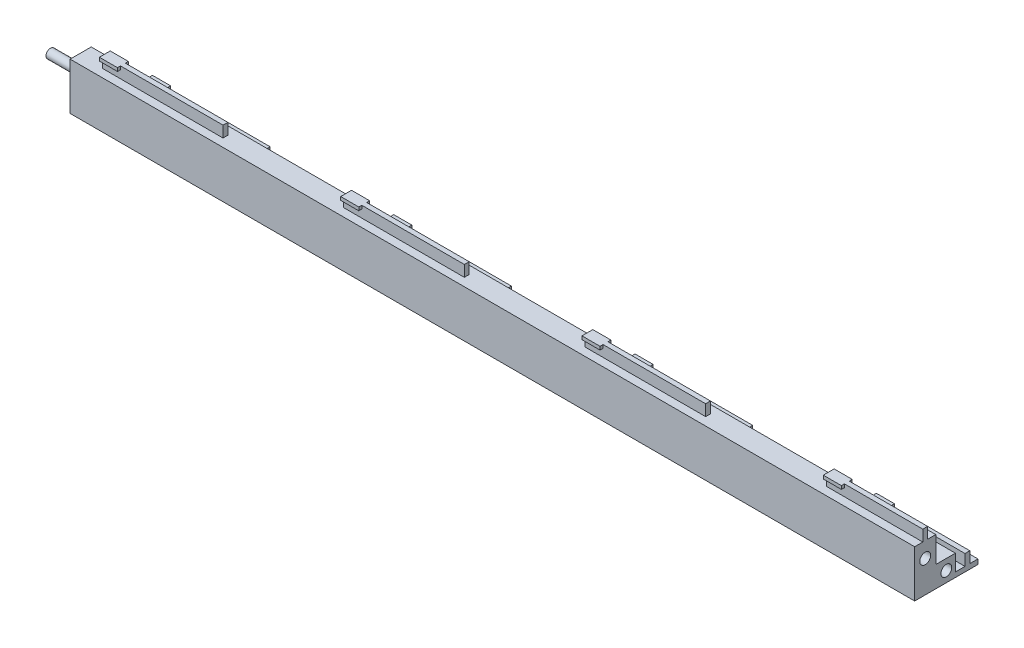
SolidWorks part; units mm, degrees
ref_plane "Front Plane" through (0, 0, 0) normal (0, 0, 1) x (1, 0, 0)
ref_plane "Top Plane" through (0, 0, 0) normal (0, 1, 0) x (1, 0, 0)
ref_plane "Right Plane" through (0, 0, 0) normal (1, 0, 0) x (0, 0, -1)
sketch "Sketch1" plane through (-58.1463, 0, 0) normal (1, 0, 0) x (0, 0, -1)
  line L1 (-13.5289, 87.3403) -> (-24.0289, 87.3403)
  line L2 (-50.0289, 87.3403) -> (-18.5289, 87.3403) construction
  line L3 (-24.0289, 87.3403) -> (-24.0289, 76.8403)
  line L4 (-24.0289, 76.8403) -> (-13.5289, 76.8403)
  line L5 (-13.5289, 82.3403) -> (-13.5289, 22.3403) construction
  line L7 (-13.5289, 76.8403) -> (-13.5289, 87.3403)
  line L8 (-20.5289, 87.3403) -> (-20.5289, 80.3403)
  line L9 (-20.5289, 80.3403) -> (-13.5289, 80.3403)
  line L10 (-24.0289, 84.6403) -> (-22.6789, 84.6403)
  line L11 (-22.6789, 84.6403) -> (-22.6789, 85.9403)
  line L12 (-22.6789, 85.9403) -> (-23.1789, 85.9403)
  line L13 (-23.1789, 85.9403) -> (-23.1789, 86.4903)
  line L14 (-23.1789, 86.4903) -> (-21.3789, 86.4903)
  line L15 (-21.3789, 86.4903) -> (-21.3789, 85.9403)
  line L16 (-21.3789, 85.9403) -> (-21.8789, 85.9403)
  line L17 (-21.8789, 85.9403) -> (-21.8789, 84.6403)
  line L18 (-21.8789, 84.6403) -> (-20.5289, 84.6403)
  line L19 (-17.0289, 77.6403) -> (-15.6789, 77.6403)
  line L20 (-15.6789, 77.6403) -> (-15.6789, 78.9403)
  line L21 (-15.6789, 78.9403) -> (-16.1789, 78.9403)
  line L22 (-16.1789, 78.9403) -> (-16.1789, 79.4903)
  line L23 (-16.1789, 79.4903) -> (-14.3789, 79.4903)
  line L24 (-14.3789, 79.4903) -> (-14.3789, 78.9403)
  line L25 (-14.3789, 78.9403) -> (-14.8789, 78.9403)
  line L26 (-14.8789, 78.9403) -> (-14.8789, 77.6403)
  line L27 (-14.8789, 77.6403) -> (-13.5289, 77.6403)
  line L28 (-24.0289, 83.8403) -> (-20.5289, 83.8403)
  line L29 (-17.0289, 80.3403) -> (-17.0289, 76.8403)
  line L30 (-17.0289, 76.8403) -> (-13.3587, 76.8403)
  circle A0 centre (-22.2789, 82.0903) radius 0.75
  circle A1 centre (-18.7789, 78.5903) radius 0.75
  circle A2 centre (-22.2789, 82.0903) radius 0.9
  circle A3 centre (-18.7789, 78.5903) radius 0.9
  point P18 (-12.6276, 76.5275)
  point P42 (0, 0)
  point P45 (0, 0)
  point P46 (-13.9157, 77.8122)
  line M11 (-13.5289, 22.3403) -> (-13.5289, 82.3403)
  dimension "D5" = 1.5
  dimension "D6" = 1.8
  dimension "D7" = 1.5
  dimension "D8" = 1.8
  dimension "D1" = 10.5
  dimension "D2" = 10.5
  dimension "D3" = 1.75
  dimension "D4" = 5.25
  dimension "D9" = 1.75
  dimension "D10" = 5.25
  dimension "D11" = 3.5
  dimension "D12" = 3.5
  dimension "D13" = 0.85
  dimension "D14" = 0.55
  dimension "D15" = 0.55
  dimension "D16" = 0.55
  dimension "D17" = 1.3
  dimension "D18" = 1.3
  dimension "D19" = 1.35
  dimension "D20" = 1.35
  dimension "D21" = 0.55
  dimension "D22" = 1.3
  dimension "D23" = 1.3
  dimension "D24" = 0.85
  dimension "D25" = 0.85
  dimension "D26" = 0.85
  dimension "D27" = 0.85
  dimension "D28" = 0.85
  dimension "D29" = 1.35
  dimension "D30" = 1.35
  dimension "D31" = 3.5
  dimension "D32" = 3.5
extrude "Boss-Extrude1" add sketch "Sketch1" along normal blind 140 contours L29 L9 L8 L28 L3 L4 L20 A3 A2 | A0 | A2 A0 | A1 | A3 A1 | L3 L28 L8 L18 L17 L16 L15 L14 L13 L12 L11 L10 | L19 L29 L4 L27 L26 L25 L24 L23 L22 L21 L20 M11 region at (-58.1463, 84.8712, 22.2789) region at (-58.1463, 79.6632, 21.206) region at (-58.1463, 77.8712, 15.2789) region at (-58.1463, 82.0903, 22.2789) region at (-58.1463, 78.5903, 18.7789) region at (-58.1463, 82.0903, 23.1534) region at (-58.1463, 78.5903, 19.6534)
extrude "Boss-Extrude2" add sketch "Sketch1<5>" against normal blind 5 contours A0 | A1 region at (-58.1463, 82.0903, 22.2789) region at (-58.1463, 78.5903, 18.7789)
sketch "Sketch1<5>" plane through (-58.1463, 0, 0) normal (1, 0, 0) x (0, 0, -1) same geometry as "Sketch1"
sketch "Sketch2" plane through (81.8537, 0, 0) normal (1, 0, 0) x (0, 0, -1)
  line L0 (-13.5289, 87.3403) -> (-24.0289, 87.3403)
  line L1 (-24.0289, 87.3403) -> (-24.0289, 76.8403)
  line L2 (-24.0289, 76.8403) -> (-13.5289, 76.8403)
  line L3 (-13.5289, 76.8403) -> (-13.5289, 87.3403)
  line L4 (-20.5289, 87.3403) -> (-20.5289, 80.3403)
  line L5 (-20.5289, 80.3403) -> (-13.5289, 80.3403)
  line L6 (-24.0289, 84.8403) -> (-22.7789, 84.8403)
  line L7 (-22.7789, 84.8403) -> (-22.7789, 85.8403)
  line L8 (-22.7789, 85.8403) -> (-23.5289, 85.8403)
  line L9 (-23.5289, 85.8403) -> (-23.5289, 86.5903)
  line L10 (-23.5289, 86.5903) -> (-21.0289, 86.5903)
  line L11 (-21.0289, 86.5903) -> (-21.0289, 85.8403)
  line L12 (-21.0289, 85.8403) -> (-21.7789, 85.8403)
  line L13 (-21.7789, 85.8403) -> (-21.7789, 84.8403)
  line L14 (-21.7789, 84.8403) -> (-20.5289, 84.8403)
  line L15 (-15.9289, 80.3403) -> (-15.9289, 78.4903)
  line L16 (-15.9289, 78.4903) -> (-17.0289, 78.4903)
  line L17 (-17.0289, 78.4903) -> (-17.0289, 77.5903)
  line L18 (-17.0289, 77.5903) -> (-13.5289, 77.5903)
  line L19 (-13.5289, 77.5903) -> (-13.5289, 78.4903)
  line L20 (-13.5289, 78.4903) -> (-14.6289, 78.4903)
  line L21 (-14.6289, 78.4903) -> (-14.6289, 80.3403)
  line L22 (-13.8789, 78.4903) -> (-13.8789, 77.5903)
  line L23 (-16.6789, 78.4903) -> (-16.6789, 77.5903)
  line L24 (-24.0289, 83.8403) -> (-20.5289, 83.8403)
  line L25 (-17.0289, 80.3403) -> (-17.0289, 76.8403)
  line L26 (-17.0289, 79.3403) -> (-13.5289, 79.3403)
  circle A0 centre (-22.2789, 82.0903) radius 0.75
  circle A1 centre (-18.7789, 78.5903) radius 0.75
  circle A2 centre (-22.2789, 82.0903) radius 0.9
  circle A3 centre (-18.7789, 78.5903) radius 0.9
  dimension "D11" = 1.5
  dimension "D12" = 1.8
  dimension "D15" = 1.5
  dimension "D16" = 1.8
  dimension "D1" = 10.5
  dimension "D2" = 10.5
  dimension "D3" = 0.75
  dimension "D4" = 0.5
  dimension "D5" = 0.5
  dimension "D6" = 1.25
  dimension "D7" = 1.25
  dimension "D8" = 1
  dimension "D9" = 1.75
  dimension "D10" = 1.75
  dimension "D13" = 1.75
  dimension "D14" = 1.75
  dimension "D17" = 3.5
  dimension "D18" = 3.5
  dimension "D19" = 3.5
  dimension "D20" = 0.75
  dimension "D21" = 0.35
  dimension "D22" = 0.35
  dimension "D23" = 1.1
  dimension "D24" = 1.1
  dimension "D25" = 1
  dimension "D26" = 0.75
  dimension "D27" = 0.75
  dimension "D28" = 1
  dimension "D29" = 1
  dimension "D30" = 0.85
  dimension "D31" = 0.85
  dimension "D32" = 2.8
  dimension "D33" = 0
extrude "Cut-Extrude1" cut sketch "Sketch2" against normal blind 6 contours A0 | A2 A0 | A1 | A3 A1 region at (81.8537, 82.0903, 22.2789) region at (81.8537, 78.5903, 18.7789) region at (81.8537, 82.0903, 23.1534) region at (81.8537, 78.5903, 19.6534)
sketch "Sketch3" plane through (81.8537, 0, 0) normal (1, 0, 0) x (0, 0, -1)
  line L0 (-17.0289, 80.3403) -> (-17.0289, 77.6403)
  line L1 (-20.5289, 80.3403) -> (-13.5289, 80.3403) construction
  line L2 (-17.0289, 77.6403) -> (-17.2789, 77.6403)
  line L3 (-17.2789, 77.6403) -> (-17.2789, 80.3403)
  line L4 (-17.2789, 80.3403) -> (-17.0289, 80.3403)
  line L5 (-17.0289, 77.6403) -> (-15.6789, 77.6403) construction
  line L6 (-17.0289, 80.3403) -> (-17.0289, 76.8403) construction
  point P5 (-17.0289, 77.6403)
  dimension "D1" = 0.25
extrude "Cut-Extrude2" cut sketch "Sketch3" against normal through all
sketch "Sketch4" plane through (0, 84.6403, 0) normal (0, 1, 0) x (1, 0, 0)
  line L0 (68.8537, -21.8789) -> (81.8537, -21.8789)
  line L1 (81.8537, -21.8789) -> (-58.1463, -21.8789) construction
  line L2 (81.8537, -21.8789) -> (81.8537, -20.5289)
  line L3 (81.8537, -20.5289) -> (-58.1463, -20.5289) construction
  line L4 (81.8537, -20.5289) -> (68.8537, -20.5289)
  line L5 (68.8537, -20.5289) -> (68.8537, -21.8789)
  line L6 (68.8537, -22.6789) -> (81.8537, -22.6789)
  line L7 (81.8537, -22.6789) -> (-58.1463, -22.6789) construction
  line L8 (81.8537, -22.6789) -> (81.8537, -24.0289)
  line L9 (81.8537, -24.0289) -> (-58.1463, -24.0289) construction
  line L10 (81.8537, -24.0289) -> (68.8537, -24.0289)
  line L11 (68.8537, -24.0289) -> (68.8537, -22.6789)
  line L12 (81.8537, -21.8789) -> (81.8537, -20.5289) construction
  line L13 (81.8537, -24.0289) -> (81.8537, -22.6789) construction
  line L14 (81.8537, -23.1789) -> (81.8537, -21.3789) construction
  line L15 (65.8537, -20.5289) -> (65.8537, -21.8789)
  line L16 (65.8537, -21.8789) -> (35.8537, -21.8789)
  line L17 (35.8537, -21.8789) -> (35.8537, -20.5289)
  line L18 (35.8537, -20.5289) -> (65.8537, -20.5289)
  line L19 (65.8537, -22.6789) -> (65.8537, -24.0289)
  line L20 (65.8537, -24.0289) -> (35.8537, -24.0289)
  line L21 (35.8537, -24.0289) -> (35.8537, -22.6789)
  line L22 (35.8537, -22.6789) -> (65.8537, -22.6789)
  line L23 (28.8537, -21.8789) -> (41.8537, -21.8789)
  line L24 (41.8537, -21.8789) -> (41.8537, -20.5289)
  line L25 (41.8537, -20.5289) -> (28.8537, -20.5289)
  line L26 (28.8537, -20.5289) -> (28.8537, -21.8789)
  line L27 (28.8537, -22.6789) -> (41.8537, -22.6789)
  line L28 (41.8537, -22.6789) -> (41.8537, -24.0289)
  line L29 (41.8537, -24.0289) -> (28.8537, -24.0289)
  line L30 (28.8537, -24.0289) -> (28.8537, -22.6789)
  line L31 (25.8537, -20.5289) -> (25.8537, -21.8789)
  line L32 (25.8537, -21.8789) -> (-4.1463, -21.8789)
  line L33 (-4.1463, -21.8789) -> (-4.1463, -20.5289)
  line L34 (-4.1463, -20.5289) -> (25.8537, -20.5289)
  line L35 (25.8537, -22.6789) -> (25.8537, -24.0289)
  line L36 (25.8537, -24.0289) -> (-4.1463, -24.0289)
  line L37 (-4.1463, -24.0289) -> (-4.1463, -22.6789)
  line L38 (-4.1463, -22.6789) -> (25.8537, -22.6789)
  line L39 (-11.1463, -21.8789) -> (1.8537, -21.8789)
  line L40 (1.8537, -21.8789) -> (1.8537, -20.5289)
  line L41 (1.8537, -20.5289) -> (-11.1463, -20.5289)
  line L42 (-11.1463, -20.5289) -> (-11.1463, -21.8789)
  line L43 (-11.1463, -22.6789) -> (1.8537, -22.6789)
  line L44 (1.8537, -22.6789) -> (1.8537, -24.0289)
  line L45 (1.8537, -24.0289) -> (-11.1463, -24.0289)
  line L46 (-11.1463, -24.0289) -> (-11.1463, -22.6789)
  line L47 (-14.1463, -20.5289) -> (-14.1463, -21.8789)
  line L48 (-14.1463, -21.8789) -> (-44.1463, -21.8789)
  line L49 (-44.1463, -21.8789) -> (-44.1463, -20.5289)
  line L50 (-44.1463, -20.5289) -> (-14.1463, -20.5289)
  line L51 (-14.1463, -22.6789) -> (-14.1463, -24.0289)
  line L52 (-14.1463, -24.0289) -> (-44.1463, -24.0289)
  line L53 (-44.1463, -24.0289) -> (-44.1463, -22.6789)
  line L54 (-44.1463, -22.6789) -> (-14.1463, -22.6789)
  line L55 (-51.1463, -21.8789) -> (-38.1463, -21.8789)
  line L56 (-38.1463, -21.8789) -> (-38.1463, -20.5289)
  line L57 (-38.1463, -20.5289) -> (-51.1463, -20.5289)
  line L58 (-51.1463, -20.5289) -> (-51.1463, -21.8789)
  line L59 (-51.1463, -22.6789) -> (-38.1463, -22.6789)
  line L60 (-38.1463, -22.6789) -> (-38.1463, -24.0289)
  line L61 (-38.1463, -24.0289) -> (-51.1463, -24.0289)
  line L62 (-51.1463, -24.0289) -> (-51.1463, -22.6789)
  line L63 (-54.1463, -20.5289) -> (-54.1463, -21.8789)
  line L64 (-54.1463, -21.8789) -> (-84.1463, -21.8789)
  line L65 (-84.1463, -21.8789) -> (-84.1463, -20.5289)
  line L66 (-84.1463, -20.5289) -> (-54.1463, -20.5289)
  line L67 (-54.1463, -22.6789) -> (-54.1463, -24.0289)
  line L68 (-54.1463, -24.0289) -> (-84.1463, -24.0289)
  line L69 (-84.1463, -24.0289) -> (-84.1463, -22.6789)
  line L70 (-84.1463, -22.6789) -> (-54.1463, -22.6789)
  line L71 (68.8537, -21.8789) -> (28.8537, -21.8789) construction
  line M1 (-58.1463, -22.6789) -> (-58.1463, -24.0289)
  line M2 (-58.1463, -24.0289) -> (81.8537, -24.0289)
  line M3 (81.8537, -24.0289) -> (81.8537, -22.6789)
  line M4 (81.8537, -22.6789) -> (-58.1463, -22.6789)
  dimension "D1" = 13
  dimension "D2" = 13
  dimension "D3" = 3
  dimension "D4" = 30
  dimension "D6" = 40
  dimension "D5" = 4
extrude "Cut-Extrude4" cut sketch "Sketch4" along normal through all contours L11 M2 M3 M4 | L24 L16 L15 L18 | L28 L20 L19 M4 | L16 L24 L18 L17 | L28 L22 L21 M2 | L25 L26 L23 L17 | L30 L21 M2 M4 | L44 L36 L35 M4 | L40 L32 L31 L34 | L32 L40 L34 L33 | L44 L38 L37 M2 | L41 L42 L39 L33 | L46 L37 M2 M4 | L56 L48 L47 L50 | L60 L52 L51 M4 | L60 L54 L53 M2 | L48 L56 L50 L49 | L57 L58 L55 L49 | L62 L53 M2 M4 | L66 L65 L64 L63 | L67 M4 M1 M2 | L0 L2 L4 L5 | L54 L51 L52 L53 region at (75.3537, 84.6403, 23.3539) region at (53.8537, 84.6403, 23.3539) region at (38.8537, 84.6403, 23.3539) region at (32.3537, 84.6403, 23.3539) region at (13.8537, 84.6403, 23.3539) region at (-1.1463, 84.6403, 23.3539) region at (-7.6463, 84.6403, 23.3539) region at (-26.1463, 84.6403, 23.3539) region at (-41.1463, 84.6403, 23.3539) region at (-47.6463, 84.6403, 23.3539) region at (-56.1463, 84.6403, 23.3539) region at (53.8537, 84.6403, 21.2039) region at (38.8537, 84.6403, 21.2039) region at (32.3537, 84.6403, 21.2039) region at (13.8537, 84.6403, 21.2039) region at (-1.1463, 84.6403, 21.2039) region at (-7.6463, 84.6403, 21.2039) region at (-26.1463, 84.6403, 21.2039) region at (-41.1463, 84.6403, 21.2039) region at (-47.6463, 84.6403, 21.2039) region at (-69.1463, 84.6403, 21.2039)
sketch "Sketch6" plane through (0, 77.6403, 0) normal (0, 1, 0) x (1, 0, 0)
  line L0 (68.8537, -14.8789) -> (81.8537, -14.8789)
  line L1 (81.8537, -14.8789) -> (81.8537, -13.5289)
  line L2 (81.8537, -13.5289) -> (68.8537, -13.5289)
  line L3 (68.8537, -13.5289) -> (68.8537, -14.8789)
  line L4 (68.8537, -15.6789) -> (81.8537, -15.6789)
  line L5 (81.8537, -15.6789) -> (81.8537, -17.0289)
  line L6 (81.8537, -17.0289) -> (68.8537, -17.0289)
  line L7 (68.8537, -17.0289) -> (68.8537, -15.6789)
  line L8 (65.8537, -13.5289) -> (65.8537, -14.8789)
  line L9 (65.8537, -14.8789) -> (35.8537, -14.8789)
  line L10 (35.8537, -14.8789) -> (35.8537, -13.5289)
  line L11 (35.8537, -13.5289) -> (65.8537, -13.5289)
  line L12 (65.8537, -15.6789) -> (65.8537, -17.0289)
  line L13 (65.8537, -17.0289) -> (35.8537, -17.0289)
  line L14 (35.8537, -17.0289) -> (35.8537, -15.6789)
  line L15 (35.8537, -15.6789) -> (65.8537, -15.6789)
  line L16 (28.8537, -14.8789) -> (41.8537, -14.8789)
  line L17 (41.8537, -14.8789) -> (41.8537, -13.5289)
  line L18 (41.8537, -13.5289) -> (28.8537, -13.5289)
  line L19 (28.8537, -13.5289) -> (28.8537, -14.8789)
  line L20 (28.8537, -15.6789) -> (41.8537, -15.6789)
  line L21 (41.8537, -15.6789) -> (41.8537, -17.0289)
  line L22 (41.8537, -17.0289) -> (28.8537, -17.0289)
  line L23 (28.8537, -17.0289) -> (28.8537, -15.6789)
  line L64 (68.8537, -14.8789) -> (28.8537, -14.8789) construction
  line L65 (28.8537, -14.8789) -> (41.8537, -14.8789)
  line L66 (41.8537, -14.8789) -> (41.8537, -13.5289)
  line L67 (41.8537, -13.5289) -> (28.8537, -13.5289)
  line L68 (28.8537, -13.5289) -> (28.8537, -14.8789)
  line L69 (28.8537, -15.6789) -> (41.8537, -15.6789)
  line L70 (41.8537, -15.6789) -> (41.8537, -17.0289)
  line L71 (41.8537, -17.0289) -> (28.8537, -17.0289)
  line L72 (28.8537, -17.0289) -> (28.8537, -15.6789)
  line L73 (25.8537, -13.5289) -> (25.8537, -14.8789)
  line L74 (25.8537, -14.8789) -> (-4.1463, -14.8789)
  line L75 (-4.1463, -14.8789) -> (-4.1463, -13.5289)
  line L76 (-4.1463, -13.5289) -> (25.8537, -13.5289)
  line L77 (25.8537, -15.6789) -> (25.8537, -17.0289)
  line L78 (25.8537, -17.0289) -> (-4.1463, -17.0289)
  line L79 (-4.1463, -17.0289) -> (-4.1463, -15.6789)
  line L80 (-4.1463, -15.6789) -> (25.8537, -15.6789)
  line L81 (-11.1463, -14.8789) -> (1.8537, -14.8789)
  line L82 (1.8537, -14.8789) -> (1.8537, -13.5289)
  line L83 (1.8537, -13.5289) -> (-11.1463, -13.5289)
  line L84 (-11.1463, -13.5289) -> (-11.1463, -14.8789)
  line L85 (-11.1463, -15.6789) -> (1.8537, -15.6789)
  line L86 (1.8537, -15.6789) -> (1.8537, -17.0289)
  line L87 (1.8537, -17.0289) -> (-11.1463, -17.0289)
  line L88 (-11.1463, -17.0289) -> (-11.1463, -15.6789)
  line L89 (28.8537, -14.8789) -> (-11.1463, -14.8789) construction
  line L90 (-11.1463, -14.8789) -> (1.8537, -14.8789)
  line L91 (1.8537, -14.8789) -> (1.8537, -13.5289)
  line L92 (1.8537, -13.5289) -> (-11.1463, -13.5289)
  line L93 (-11.1463, -13.5289) -> (-11.1463, -14.8789)
  line L94 (-11.1463, -15.6789) -> (1.8537, -15.6789)
  line L95 (1.8537, -15.6789) -> (1.8537, -17.0289)
  line L96 (1.8537, -17.0289) -> (-11.1463, -17.0289)
  line L97 (-11.1463, -17.0289) -> (-11.1463, -15.6789)
  line L98 (-14.1463, -13.5289) -> (-14.1463, -14.8789)
  line L99 (-14.1463, -14.8789) -> (-44.1463, -14.8789)
  line L100 (-44.1463, -14.8789) -> (-44.1463, -13.5289)
  line L101 (-44.1463, -13.5289) -> (-14.1463, -13.5289)
  line L102 (-14.1463, -15.6789) -> (-14.1463, -17.0289)
  line L103 (-14.1463, -17.0289) -> (-44.1463, -17.0289)
  line L104 (-44.1463, -17.0289) -> (-44.1463, -15.6789)
  line L105 (-44.1463, -15.6789) -> (-14.1463, -15.6789)
  line L106 (-51.1463, -14.8789) -> (-38.1463, -14.8789)
  line L107 (-38.1463, -14.8789) -> (-38.1463, -13.5289)
  line L108 (-38.1463, -13.5289) -> (-51.1463, -13.5289)
  line L109 (-51.1463, -13.5289) -> (-51.1463, -14.8789)
  line L110 (-51.1463, -15.6789) -> (-38.1463, -15.6789)
  line L111 (-38.1463, -15.6789) -> (-38.1463, -17.0289)
  line L112 (-38.1463, -17.0289) -> (-51.1463, -17.0289)
  line L113 (-51.1463, -17.0289) -> (-51.1463, -15.6789)
  line L114 (-11.1463, -14.8789) -> (-51.1463, -14.8789) construction
  line L115 (-51.1463, -14.8789) -> (-38.1463, -14.8789)
  line L116 (-38.1463, -14.8789) -> (-38.1463, -13.5289)
  line L117 (-38.1463, -13.5289) -> (-51.1463, -13.5289)
  line L118 (-51.1463, -13.5289) -> (-51.1463, -14.8789)
  line L119 (-51.1463, -15.6789) -> (-38.1463, -15.6789)
  line L120 (-38.1463, -15.6789) -> (-38.1463, -17.0289)
  line L121 (-38.1463, -17.0289) -> (-51.1463, -17.0289)
  line L122 (-51.1463, -17.0289) -> (-51.1463, -15.6789)
  line L123 (-54.1463, -13.5289) -> (-54.1463, -14.8789)
  line L124 (-54.1463, -14.8789) -> (-84.1463, -14.8789)
  line L125 (-84.1463, -14.8789) -> (-84.1463, -13.5289)
  line L126 (-84.1463, -13.5289) -> (-54.1463, -13.5289)
  line L127 (-54.1463, -15.6789) -> (-54.1463, -17.0289)
  line L128 (-54.1463, -17.0289) -> (-84.1463, -17.0289)
  line L129 (-84.1463, -17.0289) -> (-84.1463, -15.6789)
  line L130 (-84.1463, -15.6789) -> (-54.1463, -15.6789)
  line L131 (-91.1463, -14.8789) -> (-78.1463, -14.8789)
  line L132 (-78.1463, -14.8789) -> (-78.1463, -13.5289)
  line L133 (-78.1463, -13.5289) -> (-91.1463, -13.5289)
  line L134 (-91.1463, -13.5289) -> (-91.1463, -14.8789)
  line L135 (-91.1463, -15.6789) -> (-78.1463, -15.6789)
  line L136 (-78.1463, -15.6789) -> (-78.1463, -17.0289)
  line L137 (-78.1463, -17.0289) -> (-91.1463, -17.0289)
  line L138 (-91.1463, -17.0289) -> (-91.1463, -15.6789)
  line L139 (-51.1463, -14.8789) -> (-91.1463, -14.8789) construction
  line L140 (68.8537, -14.8789) -> (28.8537, -14.8789) construction
  line M20 (-58.1463, -13.5289) -> (-58.1463, -14.8789)
  line M21 (-58.1463, -14.8789) -> (81.8537, -14.8789)
  line M22 (81.8537, -14.8789) -> (81.8537, -13.5289)
  line M23 (81.8537, -13.5289) -> (-58.1463, -13.5289)
  dimension "D1" = 3
  dimension "D2" = 30
  dimension "D3" = 40
  dimension "D4" = 1.35
  dimension "D5" = 1.35
  dimension "D6" = 13
  dimension "D7" = 13
  dimension "D8" = 13
  dimension "D9" = 13
  dimension "D10" = 0.8
  dimension "D11" = 0.8
  dimension "D12" = 0.8
  dimension "D13" = 6
  dimension "D14" = 1.35
  dimension "D15" = 1.35
  dimension "D16" = 6
  dimension "D18" = 40
  dimension "D17" = 4
extrude "Cut-Extrude5" cut sketch "Sketch6" along normal through all contours L7 L6 L5 L4 | L3 M23 M21 M22 | L17 L9 L8 M23 | L15 L21 L13 L12 | L17 L11 L10 M21 | L21 L15 L14 L13 | L23 L22 L14 L20 | L19 L10 M23 M21 | L80 L86 L78 L77 | L82 L74 L73 M23 | L86 L80 L79 L78 | L82 L76 L75 M21 | L84 L75 M23 M21 | L88 L87 L79 L85 | L107 L99 L98 M23 | L105 L111 L103 L102 | L107 L101 L100 M21 | L111 L105 L104 L103 | L113 L112 L104 L110 | L109 L100 M23 M21 | L123 M23 M20 M21 | L130 L136 L128 L127 | L132 L124 L126 M20 region at (75.3537, 77.6403, 14.2039) region at (53.8537, 77.6403, 14.2039) region at (38.8537, 77.6403, 14.2039) region at (32.3537, 77.6403, 14.2039) region at (13.8537, 77.6403, 14.2039) region at (-1.1463, 77.6403, 14.2039) region at (-7.6463, 77.6403, 14.2039) region at (-26.1463, 77.6403, 14.2039) region at (-41.1463, 77.6403, 14.2039) region at (-47.6463, 77.6403, 14.2039) region at (-56.1463, 77.6403, 14.2039) region at (-68.1463, 77.6403, 14.2039) region at (75.3537, 77.6403, 16.3539) region at (53.8537, 77.6403, 16.3539) region at (38.8537, 77.6403, 16.3539) region at (32.3537, 77.6403, 16.3539) region at (13.8537, 77.6403, 16.3539) region at (-1.1463, 77.6403, 16.3539) region at (-7.6463, 77.6403, 16.3539) region at (-26.1463, 77.6403, 16.3539) region at (-41.1463, 77.6403, 16.3539) region at (-47.6463, 77.6403, 16.3539) region at (-66.1463, 77.6403, 16.3539)
sketch "Sketch7" plane through (0, 84.6403, 0) normal (0, 1, 0) x (1, 0, 0)
  line L0 (65.8537, -23.1789) -> (65.8537, -21.3789)
  line L1 (65.8537, -21.3789) -> (45.8537, -21.3789)
  line L2 (45.8537, -21.3789) -> (45.8537, -23.1789)
  line L3 (45.8537, -23.1789) -> (65.8537, -23.1789)
  line L4 (25.8537, -23.1789) -> (25.8537, -21.3789)
  line L5 (25.8537, -21.3789) -> (5.8537, -21.3789)
  line L6 (5.8537, -21.3789) -> (5.8537, -23.1789)
  line L7 (5.8537, -23.1789) -> (25.8537, -23.1789)
  line L8 (-14.1463, -23.1789) -> (-14.1463, -21.3789)
  line L9 (-14.1463, -21.3789) -> (-34.1463, -21.3789)
  line L10 (-34.1463, -21.3789) -> (-34.1463, -23.1789)
  line L11 (-34.1463, -23.1789) -> (-14.1463, -23.1789)
  line L12 (-54.1463, -23.1789) -> (-54.1463, -21.3789)
  line L13 (-54.1463, -21.3789) -> (-74.1463, -21.3789)
  line L14 (-74.1463, -21.3789) -> (-74.1463, -23.1789)
  line L15 (-74.1463, -23.1789) -> (-54.1463, -23.1789)
  line L16 (65.8537, -23.1789) -> (25.8537, -23.1789) construction
  dimension "D1" = 20
  dimension "D3" = 40
  dimension "D2" = 4
extrude "Cut-Extrude6" cut sketch "Sketch7" along normal through all
sketch "Sketch8" plane through (0, 77.6403, 0) normal (0, 1, 0) x (1, 0, 0)
  line L0 (65.8537, -14.3789) -> (45.8537, -14.3789)
  line L1 (45.8537, -14.3789) -> (45.8537, -16.1789)
  line L2 (45.8537, -16.1789) -> (65.8537, -16.1789)
  line L3 (65.8537, -16.1789) -> (65.8537, -14.3789)
  line L4 (25.8537, -14.3789) -> (5.8537, -14.3789)
  line L5 (5.8537, -14.3789) -> (5.8537, -16.1789)
  line L6 (5.8537, -16.1789) -> (25.8537, -16.1789)
  line L7 (25.8537, -16.1789) -> (25.8537, -14.3789)
  line L8 (-14.1463, -14.3789) -> (-34.1463, -14.3789)
  line L9 (-34.1463, -14.3789) -> (-34.1463, -16.1789)
  line L10 (-34.1463, -16.1789) -> (-14.1463, -16.1789)
  line L11 (-14.1463, -16.1789) -> (-14.1463, -14.3789)
  line L12 (-54.1463, -14.3789) -> (-74.1463, -14.3789)
  line L13 (-74.1463, -14.3789) -> (-74.1463, -16.1789)
  line L14 (-74.1463, -16.1789) -> (-54.1463, -16.1789)
  line L15 (-54.1463, -16.1789) -> (-54.1463, -14.3789)
  line L16 (65.8537, -14.3789) -> (25.8537, -14.3789) construction
  dimension "D1" = 20
  dimension "D3" = 40
  dimension "D2" = 4
extrude "Cut-Extrude7" cut sketch "Sketch8" along normal through all
